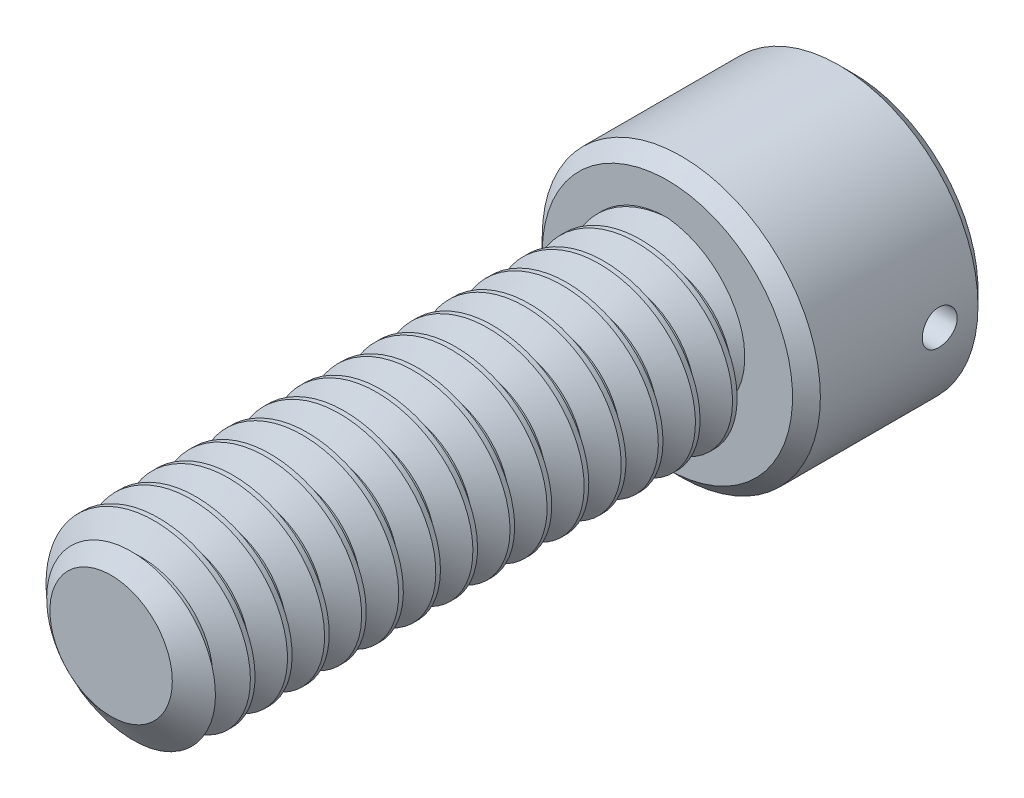
SolidWorks part; units mm, degrees
other "DetailItem1"
material "Cast Alloy Steel"
ref_plane "Front Plane" through (0, 0, 0) normal (0, 0, 1) x (1, 0, 0)
ref_plane "Top Plane" through (0, 0, 0) normal (0, 1, 0) x (1, 0, 0)
ref_plane "Right Plane" through (0, 0, 0) normal (1, 0, 0) x (0, 0, -1)
sketch "Sketch1" plane through (0, 0, 0) normal (0, 0, 1) x (1, 0, 0)
  circle A0 centre (0, 0) radius 3.175
  dimension "OD" = 6.35
extrude "Extrude1" add sketch "Sketch1" against normal blind 19.05
sketch "Sketch2" plane through (0, 0, 0) normal (0, 0, 1) x (1, 0, 0)
  circle A0 centre (0, 0) radius 3.175 construction
  circle A1 centre (0, 0) radius 3.175
curve "Helix/Spiral1" pitch 1.27 height 20.32 turns 16 parameters "pitch"=1.27
sketch "Sketch3" plane through (0, 0, 0) normal (1, 0, 0) x (0, 0, -1)
  line L0 (-1.1112, 3.175) -> (-0.635, 2.3501)
  line L1 (-0.635, 2.3501) -> (-0.4762, 2.3501)
  line L2 (-0.4762, 2.3501) -> (0, 3.175)
  line L3 (-1.1112, 3.175) -> (0, 3.175)
  line L4 (-0.5556, 3.175) -> (-0.5556, 2.3501) construction
  line L5 (-0.8731, 2.7626) -> (-0.2381, 2.7626) construction
  line L6 (0, 3.175) -> (0, -3.175) construction
  dimension "D1" = 0.1588
  dimension "D2" = 0.635
  dimension "D3" = 60
sweep "Cut-Sweep1" cut profiles "Sketch3" path "Helix/Spiral1"
sketch "Sketch4" plane through (0, 0, 0) normal (1, 0, 0) x (0, 0, -1)
  line L0 (0.7554, 3.175) -> (0, 2.0961)
  line L1 (0, 2.0961) -> (0, 3.175)
  line L2 (0.7554, 3.175) -> (0, 3.175)
  line L3 (-1.1112, 3.175) -> (0, 3.175) construction
  line L4 (0, 0) -> (7.0209, 0) construction
  dimension "D1" = 55
  dimension "D2" = 0.254
revolve "Cut-Revolve1" cut sketch "Sketch4" angle 360 about L4
sketch "Sketch6" plane through (0, 0, -19.05) normal (0, 0, -1) x (-1, 0, 0)
  circle A0 centre (0, 0) radius 4.7625
  dimension "head dia" = 9.525
extrude "Extrude2" add sketch "Sketch6" along normal blind 6.35
sketch "Sketch7" plane through (0, 0, -25.4) normal (0, 0, -1) x (-1, 0, 0)
  line L1 (0, 2.7496) -> (-2.3812, 1.3748)
  line L2 (-2.3812, 1.3748) -> (-2.3813, -1.3748)
  line L3 (-2.3813, -1.3748) -> (0, -2.7496)
  line L4 (0, -2.7496) -> (2.3813, -1.3748)
  line L5 (2.3813, -1.3748) -> (2.3813, 1.3748)
  line L6 (2.3813, 1.3748) -> (0, 2.7496)
  circle A0 centre (0, 0) radius 2.3813 construction
  dimension "hex dia" = 4.7625
extrude "Cut-Extrude1" cut sketch "Sketch7" against normal blind 3.5719
sketch "Sketch8" plane through (0, 0, -25.4) normal (0, 0, -1) x (-1, 0, 0)
  circle A0 centre (0, 0) radius 2.7496
extrude "Cut-Extrude2" cut sketch "Sketch8" against normal through all draft 45
chamfer "Chamfer1" distance 0.4763 angle 45 2 edges at (-4.7625, 0, -25.4) (-4.7625, 0, -19.05)
sketch "Sketch10" plane through (0, 0, -19.05) normal (0, 0, 1) x (1, 0, 0)
  circle A1 centre (0, 0) radius 3.175
  circle A2 centre (0, 0) radius 3.175
  dimension "D1" = 0
ref_plane "Plane1" through (0, 0, 0) normal (0, 0, 1) x (1, 0, 0)
extrude "partial thread" [suppressed] add sketch "Sketch10" along normal up to surface (19.05 mm away) separate body
chamfer "Chamfer2" [suppressed] distance 0.127 angle 45
combine bodies "Combine1" [suppressed] operation type add bodies to combine 107 108
sketch "Sketch9" plane through (0, 0, 0) normal (1, 0, 0) x (0, 0, -1)
  line L0 (0, 3.175) -> (0, -3.175) construction
  line L1 (3.175, 3.175) -> (3.175, -3.175) construction
  dimension "D1" = 3.175
sketch "Sketch12" plane through (0, 0, 0) normal (1, 0, 0) x (0, 0, -1)
  line L3 (21.8281, -1.3748) -> (21.8281, -2.7496) construction
  line L4 (21.8281, 0) -> (25.4, 0) construction
  line L5 (25.4, -4.2862) -> (25.4, 4.2862) construction
  circle A0 centre (23.6141, 0) radius 0.5969
  dimension "Wire Lock Hole" = 1.1938
extrude "Cut-Extrude3" cut sketch "Sketch12" against normal through all and the other way through all
equation "\"D3@Helix/Spiral1\" = \"screw length@Extrude1\"+\"pitch@Helix/Spiral1\""
equation "\"D1@Sketch3\" = \"pitch@Helix/Spiral1\"*.125"
equation "\"D2@Sketch3\" = \"pitch@Helix/Spiral1\"*.5"
equation "\"D1@Cut-Extrude1\" = \"hex dia@Sketch7\"*.75"
equation "\"D1@Chamfer1\" = \"head dia@Sketch6\"*.05"
equation "\"D1@Sketch9\" = \"pitch@Helix/Spiral1\"*2.5"
equation "\"D1@Chamfer2\"=\"OD@Sketch1\"*.02"
